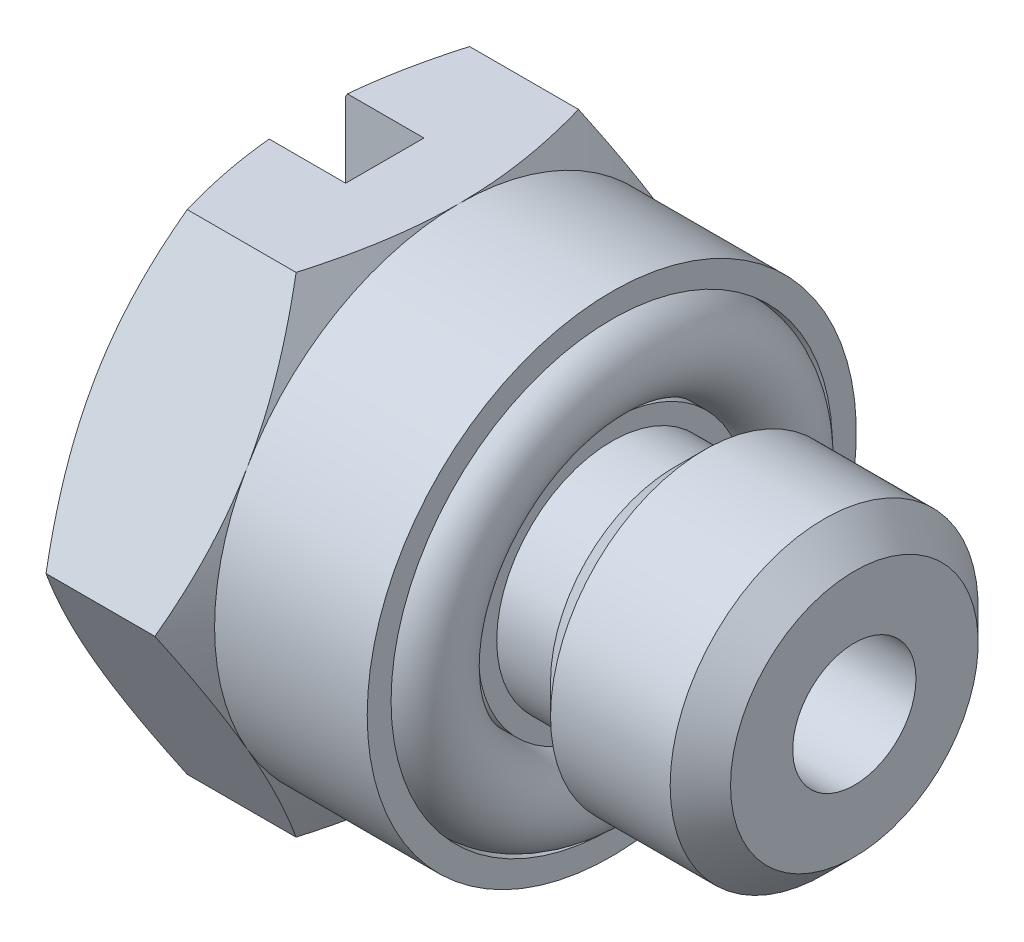
SolidWorks part; units mm, degrees
ref_plane "Front Plane" through (0, 0, 0) normal (0, 0, 1) x (1, 0, 0)
ref_plane "Top Plane" through (0, 0, 0) normal (0, 1, 0) x (1, 0, 0)
ref_plane "Right Plane" through (0, 0, 0) normal (1, 0, 0) x (0, 0, -1)
sketch "Sketch1" plane through (0, 0, 0) normal (0, 0, 1) x (1, 0, 0)
  line L0 (-3.937, 0) -> (-3.937, 1.8669)
  line L1 (-3.937, 1.8669) -> (-2.921, 1.8669)
  line L2 (-2.921, 1.8669) -> (-2.921, 2.0095)
  line L3 (-2.921, 2.0095) -> (-2.4311, 2.4994)
  line L4 (-2.4311, 2.4994) -> (-0.4899, 2.4994)
  line L5 (-0.4899, 2.4994) -> (0, 2.0095)
  line L6 (0, 2.0095) -> (0, 0)
  line L7 (0, 0) -> (-3.937, 0)
  line L8 (0, 0) -> (-3.937, 0) construction
revolve "Revolve1" add sketch "Sketch1" angle 360 about L8 reverse direction yes
cosmetic thread "Cosmetic Thread1" [suppressed] parameters "D1"=2.921, "D2"=4.019
ref_plane "Plane1" through (-3.937, 0, 0) normal (1, 0, 0) x (0, 0, -1)
sketch "Sketch2" plane through (0, 0, 0) normal (0, 0, 1) x (1, 0, 0)
  line L0 (-8.89, 0) -> (-8.89, 3.9688)
  line L1 (-8.89, 3.9688) -> (-8.1262, 5.2917)
  line L2 (-8.1262, 5.2917) -> (-7.1773, 5.2917)
  line L3 (-7.1773, 5.2917) -> (-6.4135, 3.9688)
  line L4 (-6.4135, 3.9688) -> (-3.937, 3.9688)
  line L5 (-3.937, 3.9688) -> (-3.937, 3.5814)
  line L6 (-3.937, 3.5814) -> (-4.2037, 3.5751)
  line L7 (-4.2037, 2.1717) -> (-3.937, 2.1717)
  line L8 (-3.937, 2.1717) -> (-3.937, 0)
  line L9 (-3.937, 0) -> (-8.89, 0)
  line L10 (-3.937, 0) -> (-8.89, 0) construction
  arc A0 (-4.2037, 3.5751) -> (-4.2037, 2.1717) centre (-4.2069, 2.8734) cw
revolve "Revolve2" add sketch "Sketch2" angle 360 about L10 reverse direction yes
ref_plane "Plane2" through (-8.89, 0, 0) normal (1, 0, 0) x (0, 0, -1)
sketch "Sketch3" plane through (-8.89, 0, 0) normal (1, 0, 0) x (0, 0, -1)
  line L0 (-7.9375, -7.9375) -> (7.9375, -7.9375)
  line L1 (7.9375, -7.9375) -> (7.9375, 7.9375)
  line L2 (7.9375, 7.9375) -> (-7.9375, 7.9375)
  line L3 (-7.9375, 7.9375) -> (-7.9375, -7.9375)
  line L4 (-4.5827, 0) -> (-2.2914, -3.9688)
  line L5 (-2.2914, -3.9688) -> (2.2914, -3.9688)
  line L6 (2.2914, -3.9688) -> (4.5827, 0)
  line L7 (4.5827, 0) -> (2.2914, 3.9688)
  line L8 (2.2914, 3.9688) -> (-2.2914, 3.9688)
  line L9 (-2.2914, 3.9688) -> (-4.5827, 0)
extrude "Cut-Extrude1" cut sketch "Sketch3" along normal blind 4.953
sketch "Sketch4" plane through (-8.89, 0, 0) normal (1, 0, 0) x (0, 0, -1)
  line L0 (-0.635, -3.9688) -> (0.635, -3.9688)
  line L1 (0.635, -3.9688) -> (0.635, 3.9688)
  line L2 (0.635, 3.9688) -> (-0.635, 3.9688)
  line L3 (-0.635, 3.9688) -> (-0.635, -3.9688)
extrude "Cut-Extrude2" cut sketch "Sketch4" along normal blind 1.27
ref_plane "a1 XY" through (0, 0, 0) normal (0, 0, 1) x (1, 0, 0)
ref_plane "a1 XZ" through (0, 3.9688, 0) normal (0, -1, 0) x (-1, 0, 0)
ref_plane "a1 YZ" through (-8.89, 0, 0) normal (1, 0, 0) x (0, 0, -1)
ref_axis "a1 X" through (-80.9, 3.9688, 0) along (1, 0, 0)
ref_axis "a1 Y" through (-8.89, -50, 0) along (0, 1, 0)
ref_axis "a1 Z" through (-8.89, 3.9688, 80.9) along (0, 0, -1)
sketch3d "a1"
  point P0 (-8.89, 3.9688, 0)
ref_plane "a2 XY" through (0, 0, 0) normal (0, 0, 1) x (1, 0, 0)
ref_plane "a2 XZ" through (0, 1.6662, 0) normal (0, -1, 0) x (-1, 0, 0)
ref_plane "a2 YZ" through (0, 0, 0) normal (1, 0, 0) x (0, 0, -1)
ref_axis "a2 X" through (-80.9, 1.6662, 0) along (1, 0, 0)
ref_axis "a2 Y" through (0, -50, 0) along (0, 1, 0)
ref_axis "a2 Z" through (0, 1.6662, 80.9) along (0, 0, -1)
sketch3d "a2"
  point P0 (0, 1.6662, 0)
ref_plane "b1 XY" through (0, 0, 0) normal (0, 0, 1) x (1, 0, 0)
ref_plane "b1 XZ" through (0, -3.9688, 0) normal (0, -1, 0) x (-1, 0, 0)
ref_plane "b1 YZ" through (-8.89, 0, 0) normal (1, 0, 0) x (0, 0, -1)
ref_axis "b1 X" through (-80.9, -3.9688, 0) along (1, 0, 0)
ref_axis "b1 Y" through (-8.89, -50, 0) along (0, 1, 0)
ref_axis "b1 Z" through (-8.89, -3.9688, 80.9) along (0, 0, -1)
sketch3d "b1"
  point P0 (-8.89, -3.9688, 0)
ref_plane "b2 XY" through (0, 0, 0) normal (0, 0, 1) x (1, 0, 0)
ref_plane "b2 XZ" through (0, 3.9688, 0) normal (0, -1, 0) x (-1, 0, 0)
ref_plane "b2 YZ" through (-8.89, 0, 0) normal (1, 0, 0) x (0, 0, -1)
ref_axis "b2 X" through (-80.9, 3.9688, 0) along (1, 0, 0)
ref_axis "b2 Y" through (-8.89, -50, 0) along (0, 1, 0)
ref_axis "b2 Z" through (-8.89, 3.9688, 80.9) along (0, 0, -1)
sketch3d "b2"
  point P0 (-8.89, 3.9688, 0)
ref_plane "c1 XY" through (0, 0, 0) normal (0, 0, 1) x (1, 0, 0)
ref_plane "c1 XZ" through (0, 3.9688, 0) normal (0, -1, 0) x (-1, 0, 0)
ref_plane "c1 YZ" through (-8.89, 0, 0) normal (1, 0, 0) x (0, 0, -1)
ref_axis "c1 X" through (-80.9, 3.9688, 0) along (1, 0, 0)
ref_axis "c1 Y" through (-8.89, -50, 0) along (0, 1, 0)
ref_axis "c1 Z" through (-8.89, 3.9688, 80.9) along (0, 0, -1)
sketch3d "c1"
  point P0 (-8.89, 3.9688, 0)
ref_plane "c2 XY" through (0, 0, 0) normal (0, 0, 1) x (1, 0, 0)
ref_plane "c2 XZ" through (0, 3.9688, 0) normal (0, -1, 0) x (-1, 0, 0)
ref_plane "c2 YZ" through (-3.937, 0, 0) normal (1, 0, 0) x (0, 0, -1)
ref_axis "c2 X" through (-80.9, 3.9688, 0) along (1, 0, 0)
ref_axis "c2 Y" through (-3.937, -50, 0) along (0, 1, 0)
ref_axis "c2 Z" through (-3.937, 3.9688, 80.9) along (0, 0, -1)
sketch3d "c2"
  point P0 (-3.937, 3.9688, 0)
ref_plane "ts1 XY" through (0, 0, 0) normal (0, 0, 1) x (1, 0, 0)
ref_plane "ts1 XZ" through (0, 2.4994, 0) normal (0, -1, 0) x (-1, 0, 0)
ref_plane "ts1 YZ" through (0, 0, 0) normal (1, 0, 0) x (0, 0, -1)
ref_axis "ts1 X" through (-80.9, 2.4994, 0) along (1, 0, 0)
ref_axis "ts1 Y" through (0, -50, 0) along (0, 1, 0)
ref_axis "ts1 Z" through (0, 2.4994, 80.9) along (0, 0, -1)
sketch3d "ts1"
  point P0 (0, 2.4994, 0)
ref_plane "ts2 XY" through (0, 0, 0) normal (0, 0, 1) x (1, 0, 0)
ref_plane "ts2 XZ" through (0, -2.4994, 0) normal (0, -1, 0) x (-1, 0, 0)
ref_plane "ts2 YZ" through (0, 0, 0) normal (1, 0, 0) x (0, 0, -1)
ref_axis "ts2 X" through (-80.9, -2.4994, 0) along (1, 0, 0)
ref_axis "ts2 Y" through (0, -50, 0) along (0, 1, 0)
ref_axis "ts2 Z" through (0, -2.4994, 80.9) along (0, 0, -1)
sketch3d "ts2"
  point P0 (0, -2.4994, 0)
sketch3d "3DSketch9"
  point P0 (-8.89, -3.9688, 0)
  point P1 (0, 3.9688, 0)
  point P2 (-8.89, 3.9688, 0)
  point P3 (-8.89, -3.9688, 0)
  point P4 (-8.89, 3.9688, 0)
  point P5 (-8.89, 3.9688, 0)
  point P6 (0, 1.6662, 0)
  point P7 (-8.89, 3.9688, 0)
  point P8 (-3.937, 3.9688, 0)
  point P9 (0, 2.4994, 0)
  point P10 (0, -2.4994, 0)
ref_plane "Plane27" through (0, 0, 0) normal (0, 0, 1) x (1, 0, 0)
sketch "Sketch5" plane through (0, 0, 0) normal (0, 0, 1) x (1, 0, 0)
  point P0 (-8.89, -3.9688)
  dimension "D1" = 7.9375
  dimension "D2" = 8.89
  dimension "D3" = 4.953
  dimension "D4" = 4.9987
hole_wizard "Ø0.6 (0.6) Diameter Hole1" positions "Sketch8" profile "Sketch9" hole size "Ø0.6" standard "ANSI Metric" end condition through all
sketch "Sketch8" plane through (0, 0, 0) normal (1, 0, 0) x (0, 0, -1)
  point P0 (0, 0)
sketch "Sketch9" plane through (0, 0, 0) normal (0, 1, 0) x (0, 0, -1)
  line L0 (0, 0) -> (0, 8.89)
  line L1 (0, 8.89) -> (0.3, 8.89)
  line L2 (0.3, 8.89) -> (0.3, 0)
  line L5 (0.3, 0) -> (0, 0)
  line L11 (0, -6.35) -> (0, 107.95) construction
  dimension "Thru Hole Dia." = 0.6
  dimension "Thru Hole Depth" = 8.89
sketch "Sketch10" plane through (0, 0, 0) normal (0, 0, 1) x (1, 0, 0)
  line L0 (-11.8482, 1.0905) -> (-5.947, 0.05)
  line L2 (0, 0) -> (50000, 0) construction
  line L3 (-11.8482, 1.0905) -> (-11.8482, 0)
  line L4 (-7.62, 0.345) -> (-7.62, 0) construction
  line L5 (-7.62, -3.9688) -> (-7.62, 3.9688) construction
  line L6 (-5.947, 0.05) -> (-5.947, 0)
  line L7 (-5.947, 0) -> (-11.8482, 0)
  dimension "D1" = 10
  dimension "D5" = 1.673
  dimension "D2" = 0.05
  dimension "D3" = 0.345
revolve "Cut-Revolve2" cut sketch "Sketch10" angle 360 about L2
sketch "Sketch11" [suppressed] plane through (0, 0, 0) normal (0, 1, 0) x (1, 0, 0)
  line L0 (-8.8661, 0) -> (1.6236, 1.8496)
  line L1 (1.6236, 1.8496) -> (1.6236, 0)
  line L2 (1.715, 0) -> (-8.1031, 0) construction
  line L3 (-8.8661, 0) -> (1.6236, 0)
  line L4 (-7.1647, 0.3) -> (-7.1647, 0) construction
  line L6 (-7.2847, -0.3) -> (-7.2847, 0.3) construction
  line L7 (-7.2847, -0.3) -> (-7.2847, 0.3) construction
  dimension "D1" = 10
  dimension "D2" = 0.12
revolve "Cut-Revolve3" [suppressed] cut sketch "Sketch11" angle 360 about L2
hole_wizard "Ø2.0 (2) Diameter Hole1" positions "Sketch6" profile "Sketch7" hole size "Ø2.0" standard "ANSI Metric"
sketch "Sketch6" plane through (0, 0, 0) normal (1, 0, 0) x (0, 0, -1)
  point P0 (0, 0)
sketch "Sketch7" plane through (0, 0, 0) normal (0, 1, 0) x (0, 0, -1)
  line L0 (0, 0) -> (0, 7.4409)
  line L1 (0, 7.4409) -> (1, 6.84)
  line L2 (1, 6.84) -> (1, 0)
  line L5 (1, 0) -> (0, 0)
  line L10 (0, 7.4409) -> (-1, 6.84) construction
  line L11 (0, -6.35) -> (0, 107.95) construction
  dimension "Hole Dia." = 2
  dimension "Hole Depth" = 6.84
  dimension "Drill Angle" = 118
move or copy body "Body-Move/Copy2" [suppressed] bodies to move or copy 105
move or copy body "Body-Move/Copy1" [suppressed] bodies to move or copy 105
equation "\"D3@Sketch10\"=sqr(1.3225*.09)"
